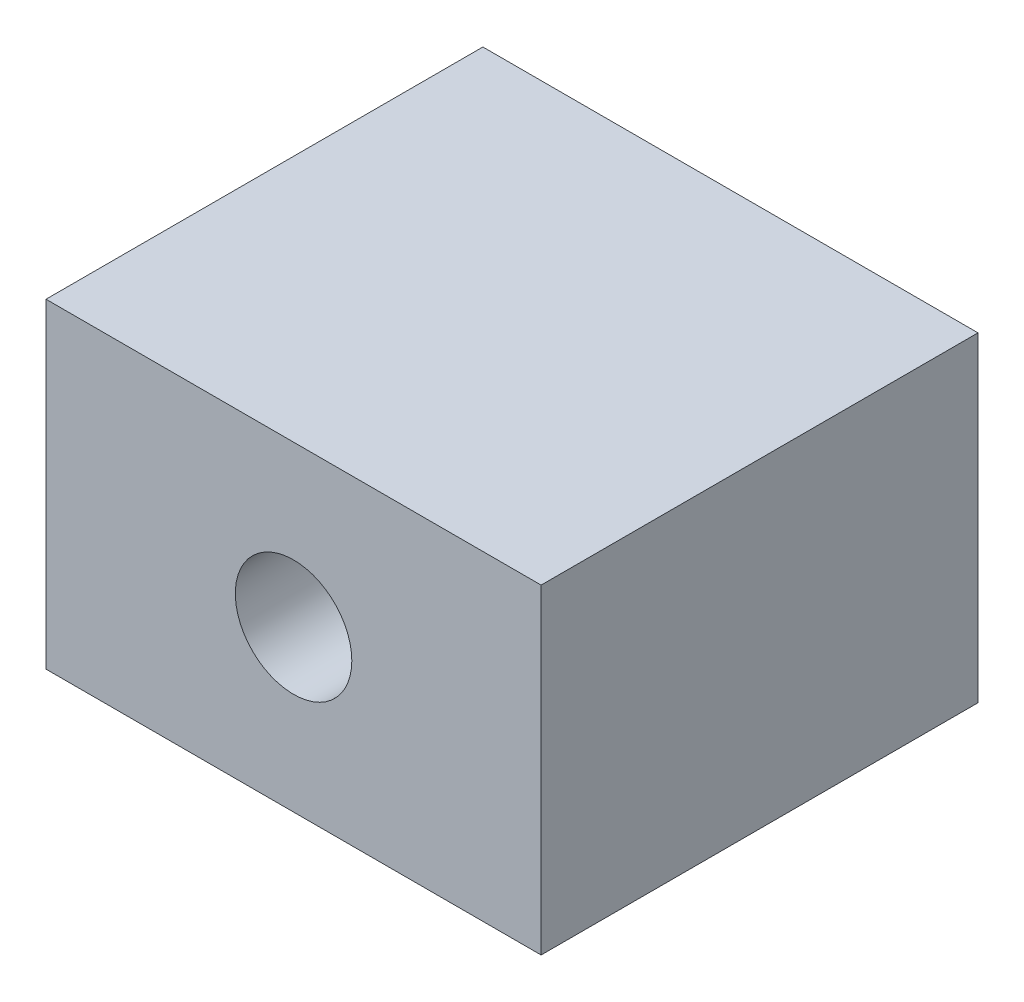
SolidWorks part; units mm, degrees
ref_plane "Front Plane" through (0, 0, 0) normal (0, 0, 1) x (1, 0, 0)
ref_plane "Top Plane" through (0, 0, 0) normal (0, 1, 0) x (1, 0, 0)
ref_plane "Right Plane" through (0, 0, 0) normal (1, 0, 0) x (0, 0, -1)
sketch "Sketch1" plane through (0, 0, 0) normal (0, 0, 1) x (1, 0, 0)
  line L0 (17, 22) -> (17, 0) construction
  line L1 (0, 0) -> (34, 0)
  line L2 (0, 0) -> (0, 22)
  line L3 (0, 22) -> (34, 22)
  line L4 (34, 0) -> (34, 22)
  circle A0 centre (17, 11) radius 4
  dimension "D4" = 8
  dimension "D1" = 34
  dimension "D2" = 22
  dimension "D3" = 11
extrude "Boss-Extrude1" add sketch "Sketch1" along normal blind 30
